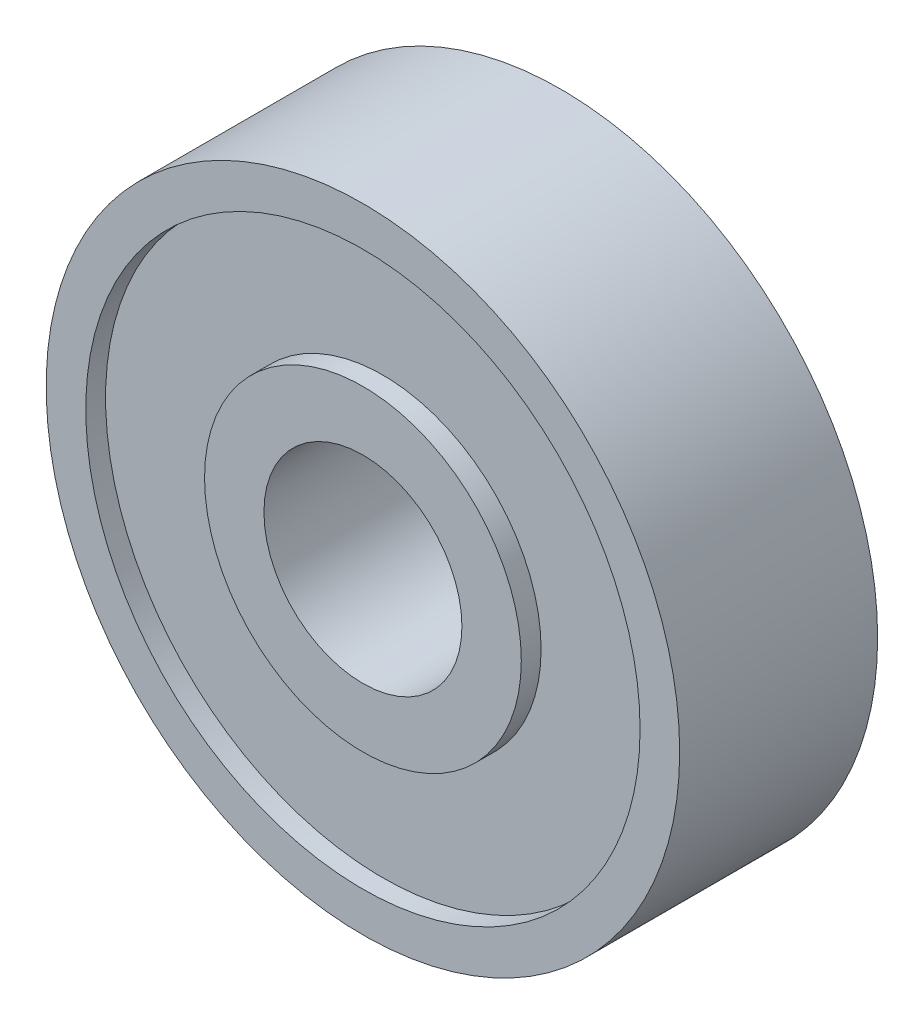
SolidWorks part; units mm, degrees
ref_plane "Plan de face" through (0, 0, 0) normal (0, 0, 1) x (1, 0, 0)
ref_plane "Plan de dessus" through (0, 0, 0) normal (0, 1, 0) x (1, 0, 0)
ref_plane "Plan de droite" through (0, 0, 0) normal (1, 0, 0) x (0, 0, -1)
sketch "Esquisse1" plane through (0, 0, 0) normal (0, 0, 1) x (1, 0, 0)
  circle A0 centre (0, 0) radius 8
  circle A1 centre (0, 0) radius 7
  circle A2 centre (0, 0) radius 4
  circle A3 centre (0, 0) radius 2.5
  dimension "D1" = 16
extrude "Boss.-Extru.1" add sketch "Esquisse1" along normal blind 5 contours A0 A1 region at (-7.7737, 0, 0)
extrude "Boss.-Extru.2" add sketch "Esquisse1<3>" along normal blind 4.5 contours A1 A2 region at (-6.802, 0, 0)
sketch "Esquisse1<3>" plane through (0, 0, 0) normal (0, 0, 1) x (1, 0, 0) same geometry as "Esquisse1"
extrude "Boss.-Extru.3" add sketch "Esquisse1<4>" along normal blind 5 contours A2 A3 region at (-3.8869, 0, 0)
sketch "Esquisse1<4>" plane through (0, 0, 0) normal (0, 0, 1) x (1, 0, 0) same geometry as "Esquisse1"
sketch "Esquisse2" plane through (0, 0, 0) normal (0, 0, -1) x (-1, 0, 0)
  circle A0 centre (0, 0) radius 7
  circle A1 centre (0, 0) radius 5
extrude "Enlèv. mat.-Extru.2" cut sketch "Esquisse2" against normal blind 0.5
